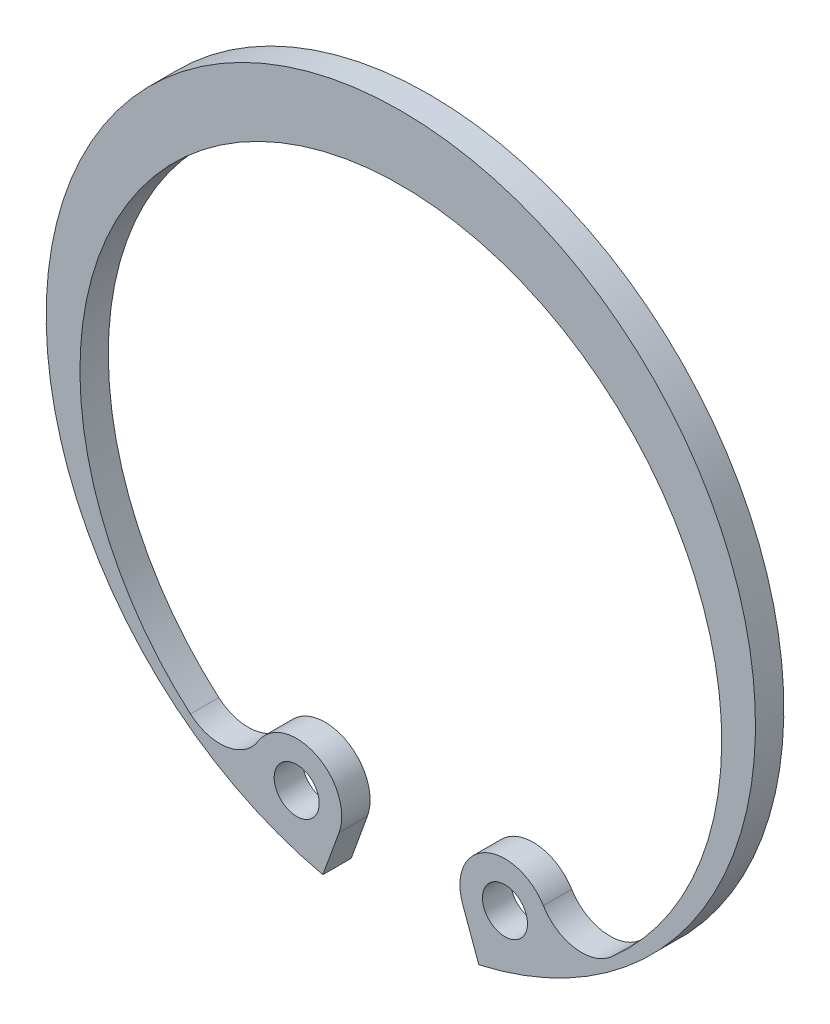
SolidWorks part; units mm, degrees
ref_plane "Front" through (0, 0, 0) normal (0, 0, 1) x (1, 0, 0)
ref_plane "Top" through (0, 0, 0) normal (0, 1, 0) x (1, 0, 0)
ref_plane "Right" through (0, 0, 0) normal (1, 0, 0) x (0, 0, -1)
ref_axis "Center Axis" through (0, 0, 1.5888) along (0, 0, -1)
sketch "Sketch1" plane through (0, 0, 0) normal (0, 0, 1) x (1, 0, 0)
  circle A0 centre (0, 0) radius 14.7
  dimension "D1" = 29.4
extrude "Extrude1" add sketch "Sketch1" along normal blind 1.175
ref_plane "Reference Plane for Front Recess" through (0, 0, 1.175) normal (0, 0, 1) x (1, 0, 0)
sketch "Sketch34" plane through (0, 0, 1.175) normal (0, 0, 1) x (1, 0, 0)
  line L0 (0, 0) -> (0, -10.6398) construction
  line L1 (0, 0) -> (-3.8763, -10.6501) construction
  line L2 (0, 0) -> (3.8763, -10.6501) construction
  line L3 (-2.5617, -12.4959) -> (-3.2329, -14.3401)
  line L4 (2.5617, -12.4959) -> (3.2329, -14.3401)
  circle A1 centre (0, 0) radius 14.7 construction
  arc A2 (3.2329, -14.3401) -> (-3.2329, -14.3401) centre (0, 0) ccw
  circle A3 centre (0, -1.27) radius 11.4333 construction
  circle A4 centre (4.3158, -11.8575) radius 0.9333
  circle A5 centre (-4.3158, -11.8575) radius 0.9333
  arc A6 (-2.5617, -12.4959) -> (-5.9061, -10.8801) centre (-4.3158, -11.8575) ccw
  arc A7 (2.5617, -12.4959) -> (5.9061, -10.8801) centre (4.3158, -11.8575) cw
  arc A9 (-8.7204, -11.3122) -> (-5.9061, -10.8801) centre (-7.4965, -9.9027) ccw
  arc A12 (8.7204, -11.3122) -> (5.9061, -10.8801) centre (7.4965, -9.9027) cw
  arc A14 (8.7204, -11.3122) -> (-8.7204, -11.3122) centre (0, -1.27) ccw
  point P0 (0, -1.27)
  dimension "D2" = 3.7333
  dimension "D5" = 1.8667
  dimension "D4" = 26.6
  dimension "D1" = 1.27
  dimension "D3" = 40
extrude "056-250 Snap Ring" add sketch "Sketch34" along normal blind 1.175
sketch "Sketch35" plane through (0, 0, 0) normal (0, 0, -1) x (-1, 0, 0)
  circle A1 centre (0, 0) radius 14.7
  circle A2 centre (0, 0) radius 14.7
  dimension "D1" = 0
extrude "Cut-Extrude1" cut sketch "Sketch35" against normal blind 1.175
